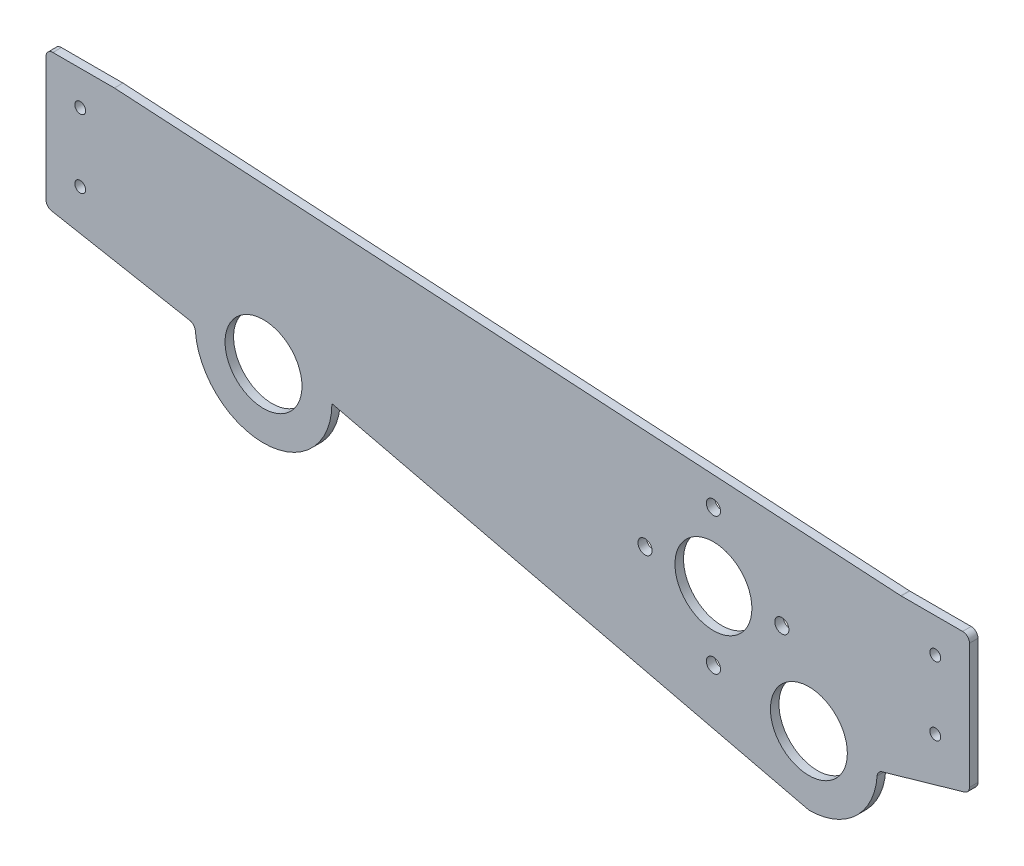
SolidWorks part; units mm, degrees
ref_plane "Front Plane" through (0, 0, 0) normal (0, 0, 1) x (1, 0, 0)
ref_plane "Top Plane" through (0, 0, 0) normal (0, 1, 0) x (1, 0, 0)
ref_plane "Right Plane" through (0, 0, 0) normal (1, 0, 0) x (0, 0, -1)
sketch "Sketch1" plane through (0, 0, 0) normal (0, 0, 1) x (1, 0, 0)
  line L0 (-101.6, -38.1991) -> (158.75, -38.1991) construction
  line L1 (-101.6, 76.1009) -> (273.6285, 76.1009) construction
  line L2 (-101.6, 164.2389) -> (101.6, 164.2389) construction
  line L3 (0, -88.9) -> (0, 235.6129) construction
  line L6 (-146.05, 113.4389) -> (-171.45, 113.4389) construction
  line L7 (-146.05, 113.4389) -> (-146.05, 164.2389) construction
  line L8 (-146.05, 164.2389) -> (-171.45, 164.2389)
  line L9 (-171.45, 113.4389) -> (-171.45, 164.2389)
  line L10 (-146.05, 113.4389) -> (-171.45, 164.2389) construction
  line L11 (-146.05, 164.2389) -> (-171.45, 113.4389) construction
  line L12 (-146.05, 164.2389) -> (146.05, 146.9669)
  line L17 (146.05, 96.1669) -> (171.45, 96.1669) construction
  line L18 (146.05, 96.1669) -> (146.05, 146.9669) construction
  line L19 (146.05, 146.9669) -> (171.45, 146.9669)
  line L20 (171.45, 96.1669) -> (171.45, 146.9669)
  line L21 (146.05, 96.1669) -> (171.45, 146.9669) construction
  line L22 (146.05, 146.9669) -> (171.45, 96.1669) construction
  line L23 (-146.05, 164.2389) -> (146.05, 146.9669)
  line L24 (-171.45, 113.4389) -> (-116.0814, 103.1319)
  line L25 (-65.2814, 103.1319) -> (111.8249, 60.956)
  line L26 (137.2249, 86.356) -> (171.45, 96.1669)
  circle A3 centre (0, 0) radius 88.9 construction
  circle A4 centre (111.8249, 86.356) radius 52.3875 construction
  circle A5 centre (-90.6814, 103.1319) radius 25.4 construction
  circle A6 centre (0, 172.7119) radius 88.9 construction
  circle A7 centre (-90.6814, 103.1319) radius 14.2875
  circle A8 centre (111.8249, 86.356) radius 14.2875
  circle A11 centre (-158.75, 151.5389) radius 2.0193
  circle A12 centre (158.75, 134.2669) radius 2.0193
  circle A13 centre (-90.6814, 103.1319) radius 23.495 construction
  circle A14 centre (111.8249, 86.356) radius 23.495 construction
  circle A15 centre (158.75, 108.8669) radius 2.0193
  circle A16 centre (-158.75, 126.1389) radius 2.0193
  arc A17 (-116.0814, 103.1319) -> (-65.2814, 103.1319) centre (-90.6814, 103.1319) ccw
  arc A18 (86.4249, 86.356) -> (137.2249, 86.356) centre (111.8249, 86.356) ccw
  point P12 (0, 164.2389)
  point P24 (-158.75, 151.5389)
  point P25 (158.75, 134.2669)
  point P37 (158.75, 121.5669)
  point P38 (5.3981, 114.787)
  point P39 (158.75, 121.5669)
  point P46 (158.75, 146.9669)
  point P48 (-158.75, 138.8389)
  point P49 (0, 0)
  point P50 (0, 0)
  point P51 (0, 0)
  point P52 (0, 0)
  dimension "D1" = 177.8
  dimension "D2" = 104.775
  dimension "D3" = 38.1991
  dimension "D5" = 50.8
  dimension "D10" = 177.8
  dimension "D12" = 28.575
  dimension "D13" = 28.575
  dimension "D14" = 4.0386
  dimension "D18" = 4.0386
  dimension "D19" = 46.99
  dimension "D20" = 46.99
  dimension "D32" = 25.4
  dimension "D33" = 25.4
  dimension "D4" = 114.3
  dimension "D6" = 203.2
  dimension "D7" = 158.75
  dimension "D8" = 203.2
  dimension "D9" = 202.438
  dimension "D11" = 260.35
  dimension "D15" = 189.738
  dimension "D16" = 317.5
  dimension "D17" = 172.466
  dimension "D22" = 12.7
  dimension "D23" = 25.4
  dimension "D24" = 12.7
  dimension "D25" = 12.7
  dimension "D26" = 25.4
  dimension "D27" = 71.374
  dimension "D28" = 50.8
  dimension "D29" = 50.8
  dimension "D30" = 12.7
  dimension "D31" = 61.107
  dimension "D21" = 2
extrude "Boss-Extrude1" add sketch "Sketch1" along normal blind 3.175 contours L20 L19 L12 L8 L9 A16 A15 A12 A11 A8 A7 region at (5.3354, 121.0495, 0)
fillet "Fillet1" radius 2.54 7 edges at (-171.45, 164.2389, 1.5875) (171.45, 146.9669, 1.5875) (171.45, 96.1669, 1.5875) (-171.45, 113.4389, 1.5875) (146.05, 146.9669, 1.5875) (137.2249, 86.356, 1.5875) (-116.0814, 103.1319, 1.5875)
sketch "Sketch2" plane through (0, 0, 3.175) normal (0, 0, 1) x (1, 0, 0)
  circle A0 centre (76.3807, 115.2355) radius 14.2875
  circle A1 centre (111.8249, 86.356) radius 14.2875 construction
  circle A2 centre (-90.6814, 103.1319) radius 14.2875 construction
  circle A3 centre (76.3807, 140.6355) radius 2.6289
  circle A4 centre (101.7807, 115.2355) radius 2.6289
  circle A5 centre (76.3807, 89.8355) radius 2.6289
  circle A6 centre (50.9807, 115.2355) radius 2.6289
  point P17 (76.3807, 115.2355)
  dimension "D3" = 28.575
  dimension "D4" = 5.2578
  dimension "D1" = 45.72
  dimension "D2" = 167.5
  dimension "D5" = 25.4
  dimension "D6" = 4
extrude "Cut-Extrude1" cut sketch "Sketch2" against normal through all
